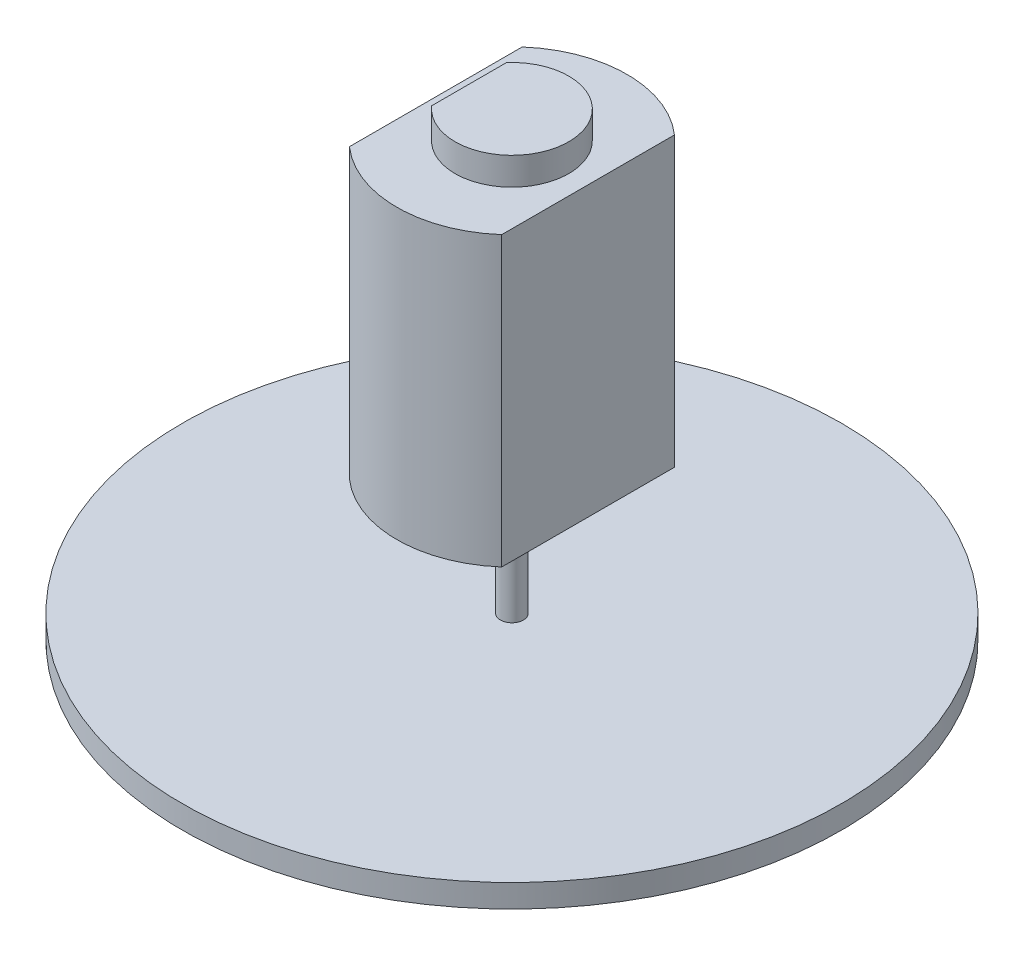
SolidWorks part; units mm, degrees
ref_plane "Front Plane" through (0, 0, 0) normal (0, 0, 1) x (1, 0, 0)
ref_plane "Top Plane" through (0, 0, 0) normal (0, 1, 0) x (1, 0, 0)
ref_plane "Right Plane" through (0, 0, 0) normal (1, 0, 0) x (0, 0, -1)
sketch "Sketch1" plane through (0, 0, 0) normal (0, 1, 0) x (1, 0, 0)
  line L2 (-6.6144, -7.5) -> (-6.6144, 7.5)
  line L4 (6.6144, -7.5) -> (6.6144, 7.5)
  arc A0 (-6.6144, -7.5) -> (6.6144, -7.5) centre (0, 0) ccw
  arc A1 (6.6144, 7.5) -> (-6.6144, 7.5) centre (0, 0) ccw
  dimension "D1" = 15
  dimension "D2" = 20
extrude "Boss-Extrude1" add sketch "Sketch1" along normal blind 25
sketch "Sketch2" plane through (0, 25, 0) normal (0, 1, 0) x (1, 0, 0)
  line L0 (-3.7204, 3.25) -> (-3.7204, -3.25)
  arc A0 (-3.7204, -3.25) -> (-3.7204, 3.25) centre (0, 0) ccw
  dimension "D1" = 9.88
  dimension "D2" = 6.5
extrude "Boss-Extrude2" add sketch "Sketch2" along normal blind 2.4
sketch "Sketch3" plane through (0, 0, 0) normal (0, -1, 0) x (1, 0, 0)
  circle A0 centre (0, 0) radius 3
  circle A1 centre (0, 0) radius 1
  dimension "D1" = 6
  dimension "D2" = 2
extrude "Boss-Extrude3" add sketch "Sketch3" along normal blind 2.3 contours A1 | A0 A1 region at (-2.9151, 0, 0) region at (0, 0, 0)
extrude "Boss-Extrude4" add sketch "Sketch3<3>" along normal blind 8.25 from surface contours A1 starting at face at (0, -2.3, -3)
sketch "Sketch3<3>" plane through (0, 0, 0) normal (0, -1, 0) x (1, 0, 0) same geometry as "Sketch3"
sketch "Sketch4" plane through (0, -10.55, 0) normal (0, -1, 0) x (-1, 0, 0)
  circle A0 centre (0, 0) radius 28.625
  dimension "D1" = 57.25
extrude "Boss-Extrude5" add sketch "Sketch4" along normal blind 2
